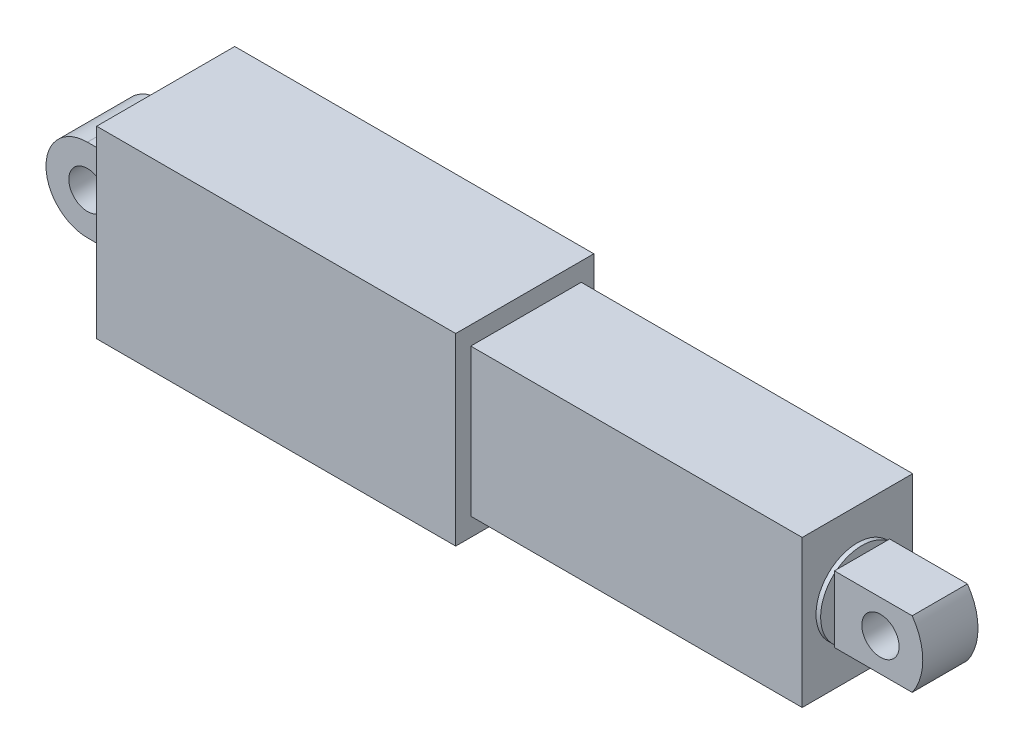
SolidWorks part; units mm, degrees
ref_plane "정면" through (0, 0, 0) normal (0, 0, 1) x (1, 0, 0)
ref_plane "윗면" through (0, 0, 0) normal (0, 1, 0) x (1, 0, 0)
ref_plane "우측면" through (0, 0, 0) normal (1, 0, 0) x (0, 0, -1)
sketch "스케치1" plane through (0, 0, 0) normal (0, 0, 1) x (1, 0, 0)
  line L5 (-19.5, 10) -> (19.5, 10)
  line L6 (-19.5, 10) -> (-19.5, -10)
  line L7 (-19.5, -10) -> (19.5, -10)
  line L8 (19.5, 10) -> (19.5, -10)
  line L9 (-19.5, 10) -> (19.5, -10) construction
  line L10 (-19.5, -10) -> (19.5, 10) construction
  point P0 (0, 0)
  dimension "D1" = 39
  dimension "D2" = 20
extrude "보스-돌출1" add sketch "스케치1" along normal blind 15
sketch "스케치2" plane through (-19.5, 0, 0) normal (-1, 0, 0) x (0, 0, 1)
  line L0 (0, 10) -> (0, -10) construction
  line L1 (3.5, 4.5) -> (11.5, 4.5)
  line L2 (3.5, 4.5) -> (3.5, -4.5)
  line L3 (3.5, -4.5) -> (11.5, -4.5)
  line L4 (11.5, 4.5) -> (11.5, -4.5)
  line L5 (3.5, 4.5) -> (11.5, -4.5) construction
  line L6 (3.5, -4.5) -> (11.5, 4.5) construction
  line L8 (15, 10) -> (0, 10) construction
  point P0 (7.5, 0)
  dimension "D1" = 7.5
  dimension "D2" = 8
  dimension "D3" = 9
  dimension "D4" = 10
extrude "보스-돌출2" add sketch "스케치2" along normal blind 9
sketch "스케치3" plane through (0, 0, 11.5) normal (0, 0, 1) x (1, 0, 0)
  line L0 (19.5, -10) -> (19.5, 10) construction
  line L1 (-28.5, 4.5) -> (-19.5, 4.5) construction
  circle A0 centre (-24, 0) radius 2.025
  dimension "D3" = 4.05
  dimension "D1" = 43.5
  dimension "D2" = 4.5
extrude "컷-돌출1" cut sketch "스케치3" against normal blind 10
fillet "필렛1" radius 4.5 2 edges at (-28.5, -4.5, 7.5) (-28.5, 4.5, 7.5)
sketch "스케치4" plane through (19.5, 0, 0) normal (1, 0, 0) x (0, 0, -1)
  line L0 (-15, 10) -> (0, 10) construction
  line L1 (-13.366, 8) -> (-1.366, 8)
  line L2 (-13.366, 8) -> (-13.366, -8)
  line L3 (-13.366, -8) -> (-1.366, -8)
  line L4 (-1.366, 8) -> (-1.366, -8)
  line L5 (-13.366, 8) -> (-1.366, -8) construction
  line L6 (-13.366, -8) -> (-1.366, 8) construction
  point P0 (-7.366, 0)
  dimension "D1" = 16
  dimension "D2" = 10
  dimension "D3" = 12
extrude "보스-돌출3" add sketch "스케치4" along normal blind 36
sketch "스케치5" plane through (55.5, 0, 0) normal (1, 0, 0) x (0, 0, -1)
  line L0 (-1.366, -8) -> (-1.366, 8) construction
  circle A0 centre (-7.366, 0) radius 4.5
  dimension "D1" = 9
  dimension "D2" = 6
extrude "보스-돌출4" add sketch "스케치5" along normal blind 0.5
ref_plane "평면1" through (0, 0, 7.366) normal (0, 0, 1) x (1, 0, 0)
sketch "스케치7" plane through (0, 0, 7.366) normal (0, 0, 1) x (1, 0, 0)
  line L0 (56, -4.5) -> (56, 4.5) construction
  line L1 (56, -3.6048) -> (64.4456, -3.6048)
  line L2 (56, -3.6048) -> (56, 3.6048)
  line L3 (56, 3.6048) -> (64.4456, 3.6048)
  arc A0 (64.4456, 3.6048) -> (64.4456, -3.6048) centre (59.3646, 0) cw
  circle A1 centre (61, 0) radius 2.025
  point P6 (59.3721, 0)
  point P10 (0, 0)
  point P11 (61.3576, 0.8466)
  point P12 (61.5912, 0.8466)
  point P13 (61.4744, 0.8884)
  point P14 (0, 0)
  dimension "D1" = 4.05
  dimension "D2" = 5
extrude "보스-돌출5" add sketch "스케치7" along normal blind 3 and the other way blind 3
